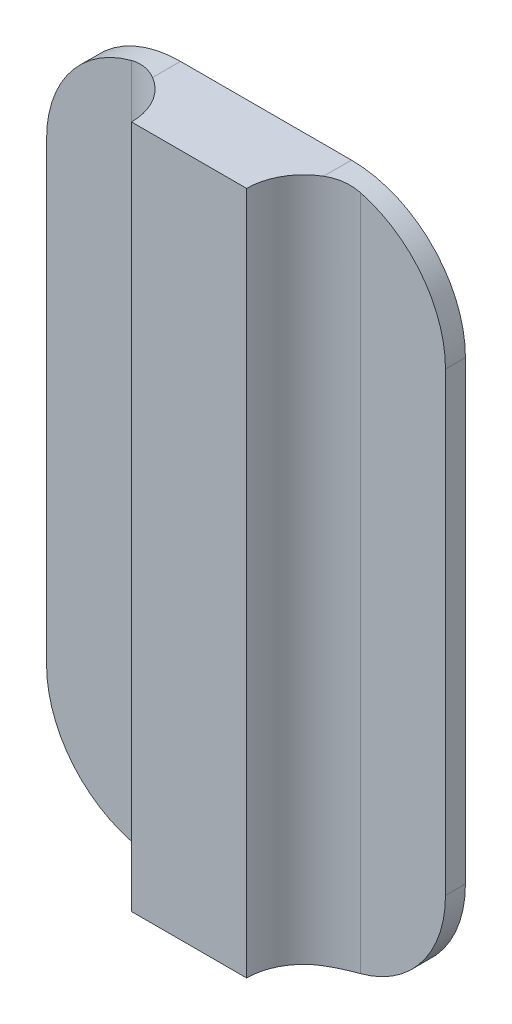
SolidWorks part; units mm, degrees
ref_plane "正面" through (0, 0, 0) normal (0, 0, 1) x (1, 0, 0)
ref_plane "平面" through (0, 0, 0) normal (0, 1, 0) x (1, 0, 0)
ref_plane "右側面" through (0, 0, 0) normal (1, 0, 0) x (0, 0, -1)
sketch "ｽｹｯﾁ1" plane through (0, 0, 0) normal (0, 0, 1) x (1, 0, 0)
  line L1 (0, 0) -> (70, 0)
  line L2 (0, 0) -> (0, 120)
  line L3 (0, 120) -> (70, 120)
  line L4 (70, 0) -> (70, 120)
  dimension "D1" = 70
  dimension "D2" = 120
extrude "ﾎﾞｽ - 押し出し1" add sketch "ｽｹｯﾁ1" along normal blind 3.5
sketch "ｽｹｯﾁ2" plane through (0, 0, 3.5) normal (0, 0, 1) x (1, 0, 0)
  line L0 (35, 120) -> (35, 0) construction
  line L1 (70, 120) -> (0, 120) construction
  line L2 (0, 0) -> (70, 0) construction
  line L4 (24.9, 0) -> (45.1, 0)
  line L5 (24.9, 0) -> (24.9, 120)
  line L6 (24.9, 120) -> (45.1, 120)
  line L7 (45.1, 0) -> (45.1, 120)
  line L8 (24.9, 0) -> (45.1, 120) construction
  line L9 (24.9, 120) -> (45.1, 0) construction
  point P6 (35, 60)
  dimension "D1" = 20.2
extrude "ﾎﾞｽ - 押し出し2" add sketch "ｽｹｯﾁ2" along normal blind 10
fillet "ﾌｨﾚｯﾄ1" radius 10 2 edges at (24.9, 60, 3.5) (45.1, 60, 3.5)
fillet "ﾌｨﾚｯﾄ2" radius 20 4 edges at (70, 120, 1.75) (70, 0, 1.75) (0, 0, 1.75) (0, 120, 1.75)
